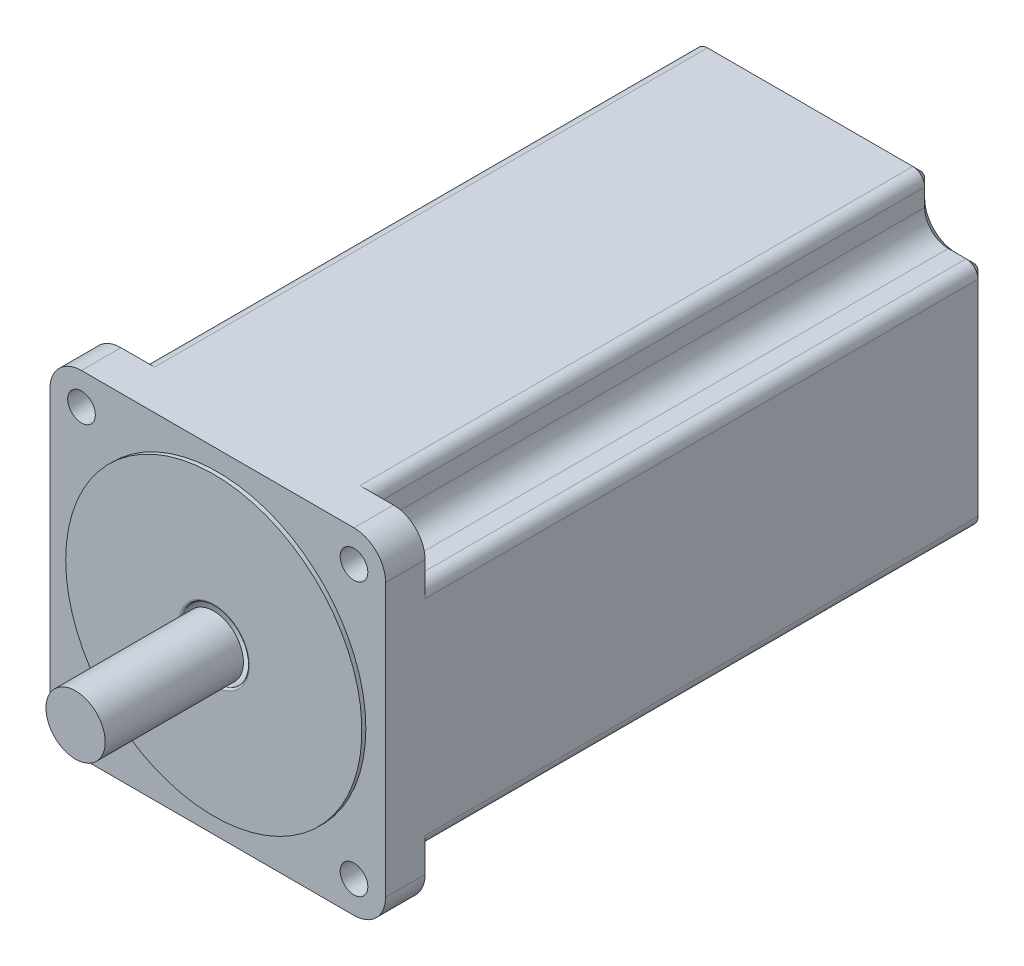
SolidWorks part; units mm, degrees
ref_plane "Front Plane" through (0, 0, 0) normal (0, 0, 1) x (1, 0, 0)
ref_plane "Top Plane" through (0, 0, 0) normal (0, 1, 0) x (1, 0, 0)
ref_plane "Right Plane" through (0, 0, 0) normal (1, 0, 0) x (0, 0, -1)
ref_plane "Plane1" through (42.5, 0, 0) normal (1, 0, 0) x (0, 0, -1)
sketch "Sketch1" plane through (42.5, 0, 0) normal (1, 0, 0) x (0, 0, -1)
  line L0 (-152, -42.5) -> (0, -42.5)
  line L1 (0, -42.5) -> (0, 42.5)
  line L2 (0, 42.5) -> (-152, 42.5)
  line L3 (-152, 42.5) -> (-152, -42.5)
extrude "Boss-Extrude1" add sketch "Sketch1" against normal blind 85
sketch "Sketch2" plane through (0, 0, 0) normal (0, 0, -1) x (-1, 0, 0)
  line L0 (-29, -42.5) -> (-29, -29)
  line L1 (-29, -29) -> (-42.5, -29)
  line L2 (-42.5, -29) -> (-42.5, -42.5)
  line L3 (-42.5, -42.5) -> (-29, -42.5)
extrude "Cut-Extrude1" cut sketch "Sketch2" against normal blind 142
sketch "Sketch3" plane through (0, 0, 0) normal (0, 0, -1) x (-1, 0, 0)
  line L0 (42.5, -29) -> (29, -29)
  line L1 (29, -29) -> (29, -42.5)
  line L2 (29, -42.5) -> (42.5, -42.5)
  line L3 (42.5, -42.5) -> (42.5, -29)
extrude "Cut-Extrude2" cut sketch "Sketch3" against normal blind 142
sketch "Sketch4" plane through (0, 0, 0) normal (0, 0, -1) x (-1, 0, 0)
  line L0 (-42.5, 42.5) -> (-42.5, 29)
  line L1 (-42.5, 29) -> (-29, 29)
  line L2 (-29, 29) -> (-29, 42.5)
  line L3 (-29, 42.5) -> (-42.5, 42.5)
extrude "Cut-Extrude3" cut sketch "Sketch4" against normal blind 142
sketch "Sketch5" plane through (0, 0, 0) normal (0, 0, -1) x (-1, 0, 0)
  line L0 (29, 42.5) -> (29, 29)
  line L1 (29, 29) -> (42.5, 29)
  line L2 (42.5, 29) -> (42.5, 42.5)
  line L3 (42.5, 42.5) -> (29, 42.5)
extrude "Cut-Extrude4" cut sketch "Sketch5" against normal blind 142
ref_plane "Plane2" through (0, 0, 0) normal (0, -1, 0) x (1, 0, 0)
sketch "Sketch6" plane through (0, 0, 0) normal (0, -1, 0) x (1, 0, 0)
  line L0 (37.5, 153) -> (0, 153)
  line L1 (0, 153) -> (0, 152)
  line L2 (0, 152) -> (37.5, 152)
  line L3 (37.5, 152) -> (37.5, 153)
  line L4 (0, 153) -> (0, 152) construction
revolve "Revolve1" add sketch "Sketch6" angle 360 about L4 reverse direction yes
hole_wizard "Ø7.0 (7) Diameter Hole1" positions "Sketch8" profile "Sketch7" hole size "Ø7.0" standard "ANSI Metric"
sketch "Sketch8" plane through (0, 0, 152) normal (0, 0, 1) x (1, 0, 0)
  point P0 (34.5, 34.5)
  point P1 (34.5, -34.5)
  point P2 (-34.5, -34.5)
  point P3 (-34.5, 34.5)
sketch "Sketch7" plane through (34.5, 34.5, 152) normal (1, 0, 0) x (0, -1, 0)
  line L0 (0, 0) -> (0, 152)
  line L1 (0, 152) -> (3.5, 152)
  line L2 (3.5, 152) -> (3.5, 0)
  line L5 (3.5, 0) -> (0, 0)
  line L11 (0, -6.35) -> (0, 107.95) construction
  dimension "Thru Hole Dia." = 7
  dimension "Thru Hole Depth" = 152
hole_wizard "Ø17.0 (17) Diameter Hole1" positions "Sketch10" profile "Sketch9" hole size "Ø17.0" standard "ANSI Metric"
sketch "Sketch10" plane through (0, 0, 153) normal (0, 0, 1) x (1, 0, 0)
  point P0 (0, 0)
sketch "Sketch9" plane through (0, 0, 153) normal (1, 0, 0) x (0, -1, 0)
  line L0 (0, 0) -> (0, 140)
  line L1 (0, 140) -> (8.5, 140)
  line L2 (8.5, 140) -> (8.5, 0)
  line L5 (8.5, 0) -> (0, 0)
  line L10 (0, 140) -> (-8.5, 140) construction
  line L11 (0, -6.35) -> (0, 107.95) construction
  dimension "Hole Dia." = 17
  dimension "Hole Depth" = 140
  dimension "Drill Angle" = 180
fillet "Fillet1" radius 3 8 edges at (-42.5, 29, 71) (42.5, -29, 71) (-29, 42.5, 71) (42.5, 29, 71) (29, -42.5, 71) (-29, -42.5, 71) (-42.5, -29, 71) (29, 42.5, 71) tangent propagation no
fillet "Fillet2" radius 6 4 edges at (-29, 29, 71) (-29, -29, 71) (29, -29, 71) (29, 29, 71) tangent propagation no
chamfer "Chamfer1" distance 2 angle 45 24 edges at (-30.7574, -30.7574, 0) (-29, -37.25, 0) (-37.25, -29, 0) (-28.1213, -41.6213, 0) (-41.6213, -28.1213, 0) (0, -42.5, 0) (-42.5, 0, 0) (28.1213, -41.6213, 0) (-41.6213, 28.1213, 0) (29, -37.25, 0) (-37.25, 29, 0) (30.7574, -30.7574, 0) (-30.7574, 30.7574, 0) (37.25, -29, 0) (-29, 37.25, 0) (41.6213, -28.1213, 0) (-28.1213, 41.6213, 0) (42.5, 0, 0) (0, 42.5, 0) (41.6213, 28.1213, 0) (28.1213, 41.6213, 0) (37.25, 29, 0) (29, 37.25, 0) (30.7574, 30.7574, 0)
fillet "Fillet3" radius 0.5 1 edges at (8.5, 0, 153) tangent propagation no
fillet "Fillet4" radius 8 4 edges at (-42.5, -42.5, 147) (42.5, -42.5, 147) (-42.5, 42.5, 147) (42.5, 42.5, 147) tangent propagation no
sketch "Sketch11" plane through (0, 0, 153) normal (0, 0, 1) x (1, 0, 0)
  circle A0 centre (0, 0) radius 7.5
  dimension "D1" = 15
extrude "Boss-Extrude2" add sketch "Sketch11" along normal blind 35 separate body
